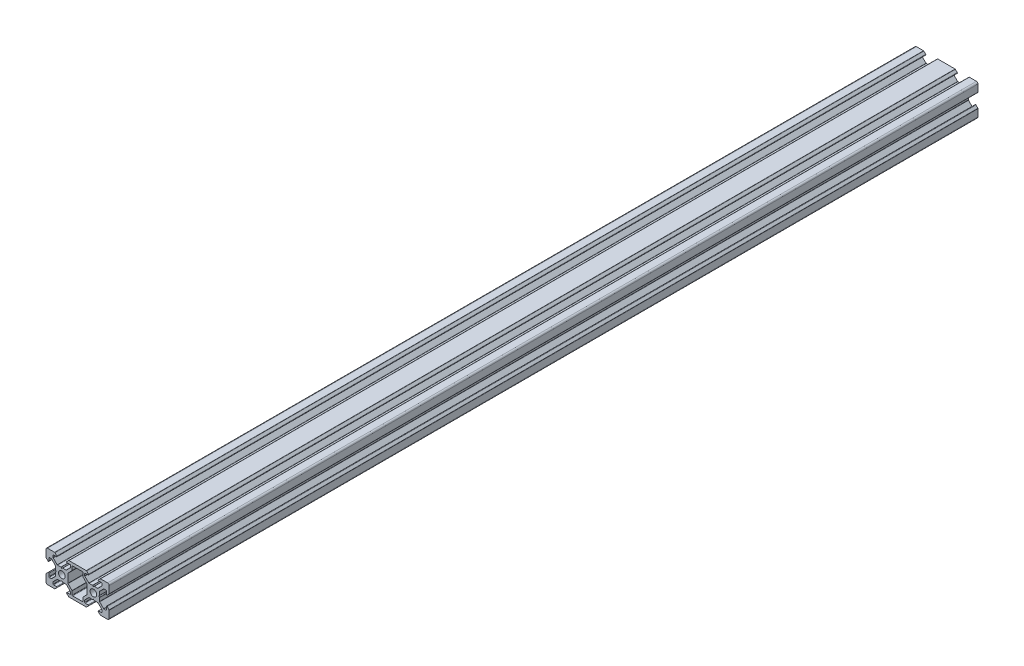
SolidWorks part; units mm, degrees
material "АД31Т ГОСТ 4784-97"
ref_plane "Спереди" through (0, 0, 0) normal (0, 0, 1) x (1, 0, 0)
ref_plane "Сверху" through (0, 0, 0) normal (0, 1, 0) x (1, 0, 0)
ref_plane "Справа" through (0, 0, 0) normal (1, 0, 0) x (0, 0, -1)
sketch "Эскиз1" plane through (0, 0, 0) normal (0, 0, 1) x (1, 0, 0)
  line L0 (12.9654, 0) -> (-12.9654, 0) construction
  line L1 (0, -12.9654) -> (0, 12.9654) construction
  line L2 (0, 0) -> (-18.3359, -18.3359) construction
  line L3 (-10, -10) -> (-10, -4.4)
  line L4 (-10, -4.4) -> (-8.2, -2.6)
  line L5 (-8.2, -2.6) -> (-8.2, -5.4993)
  line L6 (-8.2, -5.4993) -> (-6.56, -5.4993)
  line L7 (-6.56, -5.4993) -> (-3.9007, -2.84)
  line L8 (-3.9007, -2.84) -> (-3.9007, -0.5)
  line L9 (-3.9007, -0.5) -> (-3.4007, 0)
  line L10 (-0.5, -3.9007) -> (0, -3.4007)
  line L11 (-2.84, -3.9007) -> (-0.5, -3.9007)
  line L12 (-5.4993, -6.56) -> (-2.84, -3.9007)
  line L13 (-5.4993, -8.2) -> (-5.4993, -6.56)
  line L14 (-2.6, -8.2) -> (-5.4993, -8.2)
  line L15 (-4.4, -10) -> (-2.6, -8.2)
  line L16 (-10, -10) -> (-4.4, -10)
  line L17 (-10, 10) -> (-4.4, 10)
  line L18 (-4.4, 10) -> (-2.6, 8.2)
  line L19 (-2.6, 8.2) -> (-5.4993, 8.2)
  line L20 (-5.4993, 8.2) -> (-5.4993, 6.56)
  line L21 (-5.4993, 6.56) -> (-2.84, 3.9007)
  line L22 (-2.84, 3.9007) -> (-0.5, 3.9007)
  line L23 (-0.5, 3.9007) -> (0, 3.4007)
  line L24 (-3.9007, 0.5) -> (-3.4007, 0)
  line L25 (-3.9007, 2.84) -> (-3.9007, 0.5)
  line L26 (-6.56, 5.4993) -> (-3.9007, 2.84)
  line L27 (-8.2, 5.4993) -> (-6.56, 5.4993)
  line L28 (-8.2, 2.6) -> (-8.2, 5.4993)
  line L29 (-10, 4.4) -> (-8.2, 2.6)
  line L30 (-10, 10) -> (-10, 4.4)
  line L31 (0.5, 3.9007) -> (0, 3.4007)
  line L32 (0.5, -3.9007) -> (0, -3.4007)
  line L33 (10, -10) -> (10, 10) construction
  line L34 (3.9007, -0.5) -> (3.9007, 0.5)
  line L35 (6.56, -5.4993) -> (6.56, -8.2)
  line L36 (13.44, -5.4993) -> (16.0993, -2.84)
  line L37 (6.56, 5.4993) -> (3.9007, 2.84)
  line L38 (3.9007, 2.84) -> (3.9007, 0.5)
  line L39 (6.56, -8.2) -> (13.44, -8.2)
  line L40 (2.84, 3.9007) -> (0.5, 3.9007)
  line L41 (5.4993, 6.56) -> (2.84, 3.9007)
  line L42 (5.4993, 8.2) -> (5.4993, 6.56)
  line L43 (2.6, 8.2) -> (5.4993, 8.2)
  line L44 (4.4, 10) -> (2.6, 8.2)
  line L45 (15.6, 10) -> (4.4, 10)
  line L46 (15.6, -10) -> (4.4, -10)
  line L47 (4.4, -10) -> (2.6, -8.2)
  line L48 (2.6, -8.2) -> (5.4993, -8.2)
  line L49 (5.4993, -8.2) -> (5.4993, -6.56)
  line L50 (5.4993, -6.56) -> (2.84, -3.9007)
  line L51 (2.84, -3.9007) -> (0.5, -3.9007)
  line L52 (6.56, 5.4993) -> (6.56, 8.2)
  line L53 (3.9007, -2.84) -> (3.9007, -0.5)
  line L54 (6.56, -5.4993) -> (3.9007, -2.84)
  line L55 (16.0993, -2.84) -> (16.0993, -0.5)
  line L56 (6.56, 8.2) -> (13.44, 8.2)
  line L57 (13.44, 5.4993) -> (13.44, 8.2)
  line L58 (17.16, -3.9007) -> (19.5, -3.9007)
  line L59 (14.5007, -6.56) -> (17.16, -3.9007)
  line L60 (14.5007, -8.2) -> (14.5007, -6.56)
  line L61 (17.4, -8.2) -> (14.5007, -8.2)
  line L62 (15.6, -10) -> (17.4, -8.2)
  line L63 (15.6, 10) -> (17.4, 8.2)
  line L64 (17.4, 8.2) -> (14.5007, 8.2)
  line L65 (14.5007, 8.2) -> (14.5007, 6.56)
  line L66 (14.5007, 6.56) -> (17.16, 3.9007)
  line L67 (17.16, 3.9007) -> (19.5, 3.9007)
  line L68 (16.0993, 2.84) -> (16.0993, 0.5)
  line L69 (13.44, 5.4993) -> (16.0993, 2.84)
  line L70 (13.44, -5.4993) -> (13.44, -8.2)
  line L71 (16.0993, -0.5) -> (16.0993, 0.5)
  line L72 (19.5, -3.9007) -> (20, -3.4007)
  line L73 (19.5, 3.9007) -> (20, 3.4007)
  line L74 (30, 10) -> (30, 4.4)
  line L75 (30, 4.4) -> (28.2, 2.6)
  line L76 (28.2, 2.6) -> (28.2, 5.4993)
  line L77 (28.2, 5.4993) -> (26.56, 5.4993)
  line L78 (26.56, 5.4993) -> (23.9007, 2.84)
  line L79 (23.9007, 2.84) -> (23.9007, 0.5)
  line L80 (23.9007, 0.5) -> (23.4007, 0)
  line L81 (20.5, 3.9007) -> (20, 3.4007)
  line L82 (22.84, 3.9007) -> (20.5, 3.9007)
  line L83 (25.4993, 6.56) -> (22.84, 3.9007)
  line L84 (25.4993, 8.2) -> (25.4993, 6.56)
  line L85 (22.6, 8.2) -> (25.4993, 8.2)
  line L86 (24.4, 10) -> (22.6, 8.2)
  line L87 (30, 10) -> (24.4, 10)
  line L88 (30, -10) -> (24.4, -10)
  line L89 (24.4, -10) -> (22.6, -8.2)
  line L90 (22.6, -8.2) -> (25.4993, -8.2)
  line L91 (25.4993, -8.2) -> (25.4993, -6.56)
  line L92 (25.4993, -6.56) -> (22.84, -3.9007)
  line L93 (22.84, -3.9007) -> (20.5, -3.9007)
  line L94 (20.5, -3.9007) -> (20, -3.4007)
  line L95 (23.9007, -0.5) -> (23.4007, 0)
  line L96 (23.9007, -2.84) -> (23.9007, -0.5)
  line L97 (26.56, -5.4993) -> (23.9007, -2.84)
  line L98 (28.2, -5.4993) -> (26.56, -5.4993)
  line L99 (28.2, -2.6) -> (28.2, -5.4993)
  line L100 (30, -4.4) -> (28.2, -2.6)
  line L101 (30, -10) -> (30, -4.4)
  circle A0 centre (0, 0) radius 2.1
  circle A1 centre (20, 0) radius 2.1
  point P62 (10, 8.2)
  point P80 (10, -8.2)
  dimension "D5" = 2.6
  dimension "D10" = 4.2
  dimension "D2" = 10
  dimension "D3" = 1.64
  dimension "D4" = 1.5
  dimension "D6" = 1.8
  dimension "D7" = 2.84
  dimension "D8" = 0.5
  dimension "D9" = 45
extrude "Бобышка-Вытянуть1" add sketch "Эскиз1" along normal blind 550
fillet "Скругление1" radius 1 4 edges at (-10, 10, 275) (-10, -10, 275) (30, 10, 275) (30, -10, 275)
fillet "Скругление2" radius 0.3 83 edges at (-4.4, 10, 275) (-2.6, 8.2, 275) (-5.4993, 8.2, 275) (-5.4993, 6.56, 275) (-2.84, 3.9007, 275) (-0.5, 3.9007, 275) (0.5, 3.9007, 275) (2.84, 3.9007, 275) (5.4993, 6.56, 275) (4.4, 10, 275) (5.4993, 8.2, 275) (2.6, 8.2, 275) (3.9007, 2.84, 275) (3.9007, -2.84, 275) (4.4, -10, 275) (2.6, -8.2, 275) (5.4993, -8.2, 275) (5.4993, -6.56, 275) (2.84, -3.9007, 275) (0.5, -3.9007, 275) (-0.5, -3.9007, 275) (-2.84, -3.9007, 275) (-5.4993, -6.56, 275) (-5.4993, -8.2, 275) (-2.6, -8.2, 275) (-10, -4.4, 275) (-8.2, -2.6, 275) (-8.2, -5.4993, 275) (-6.56, -5.4993, 275) (-3.9007, -2.84, 275) (-3.9007, -0.5, 275) (-3.9007, 0.5, 275) (-3.9007, 2.84, 275) (-6.56, 5.4993, 275) (-8.2, 5.4993, 275) (-8.2, 2.6, 275) (-10, 4.4, 275) (6.56, -5.4993, 275) (6.56, 5.4993, 275) (6.56, 8.2, 275) (13.44, 8.2, 275) (13.44, 5.4993, 275) (16.0993, 2.84, 275) (16.0993, -2.84, 275) (13.44, -5.4993, 275) (13.44, -8.2, 275) (6.56, -8.2, 275) (15.6, 10, 275) (17.4, 8.2, 275) (14.5007, 8.2, 275) (14.5007, 6.56, 275) (17.16, 3.9007, 275) (19.5, 3.9007, 275) (20.5, 3.9007, 275) (22.84, 3.9007, 275) (25.4993, 6.56, 275) (25.4993, 8.2, 275) (22.6, 8.2, 275) (24.4, 10, 275) (30, 4.4, 275) (28.2, 2.6, 275) (28.2, 5.4993, 275) (26.56, 5.4993, 275) (23.9007, 2.84, 275) (23.9007, 0.5, 275) (23.9007, -0.5, 275) (23.9007, -2.84, 275) (26.56, -5.4993, 275) (28.2, -5.4993, 275) (28.2, -2.6, 275) (30, -4.4, 275) (24.4, -10, 275) (22.6, -8.2, 275) (25.4993, -8.2, 275) (25.4993, -6.56, 275) (22.84, -3.9007, 275) (20.5, -3.9007, 275) (19.5, -3.9007, 275) (17.16, -3.9007, 275) (14.5007, -6.56, 275) (14.5007, -8.2, 275) (17.4, -8.2, 275) (15.6, -10, 275)
